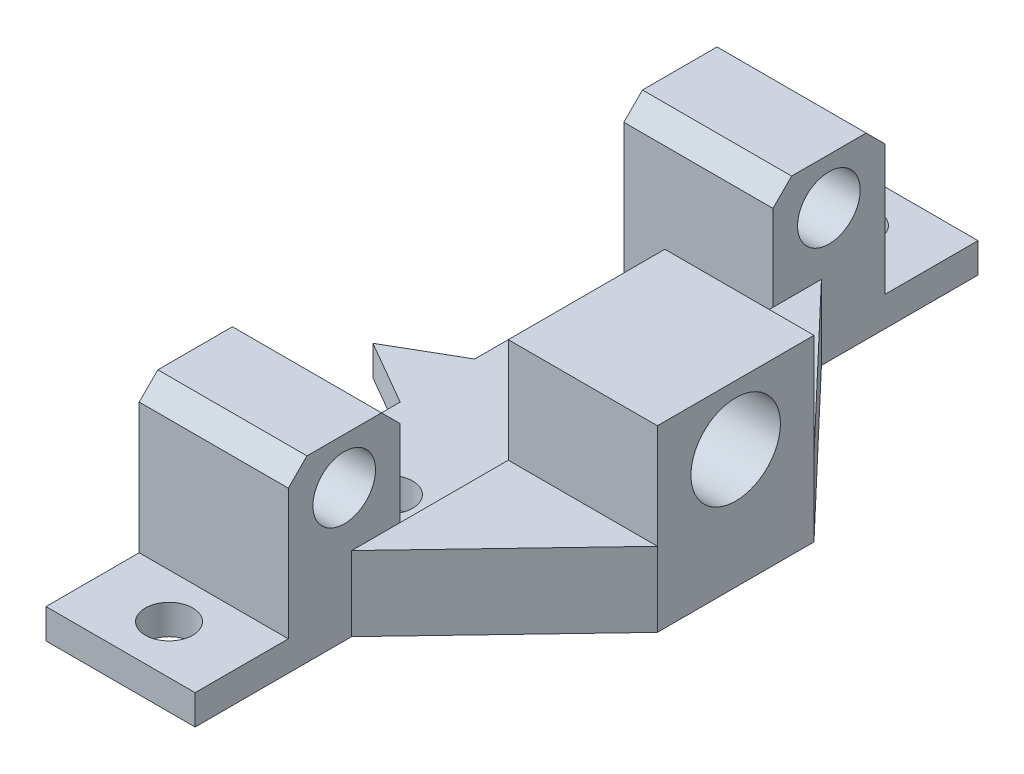
SolidWorks part; units mm, degrees
ref_plane "Front Plane" through (0, 0, 0) normal (0, 0, 1) x (1, 0, 0)
ref_plane "Top Plane" through (0, 0, 0) normal (0, 1, 0) x (1, 0, 0)
ref_plane "Right Plane" through (0, 0, 0) normal (1, 0, 0) x (0, 0, -1)
sketch "Sketch1" plane through (0, 0, 0) normal (0, 1, 0) x (1, 0, 0)
  line L1 (0, 0) -> (20, 0)
  line L2 (0, 0) -> (0, 105)
  line L3 (0, 105) -> (20, 105)
  line L4 (20, 0) -> (20, 105)
  dimension "D1" = 105
  dimension "D2" = 20
extrude "Boss-Extrude1" add sketch "Sketch1" along normal blind 4
sketch "Sketch2" plane through (0, 0, 0) normal (-1, 0, 0) x (0, 0, 1)
  line L0 (-105, 0) -> (0, 0) construction
  line L5 (-12.5, 21.5) -> (-15, 24)
  line L6 (-92.5, 0) -> (-77.5, 0)
  line L7 (-92.5, 0) -> (-92.5, 24)
  line L8 (-92.5, 24) -> (-77.5, 24)
  line L9 (-77.5, 0) -> (-77.5, 24)
  line L10 (-105, 0) -> (-92.5, 0) construction
  line L11 (-80, 24) -> (-77.5, 21.5)
  line L12 (-92.5, 21.5) -> (-90, 24)
  line L13 (-52.5, 0) -> (-52.5, 4) construction
  line L14 (-25, 24) -> (-27.5, 21.5)
  line L15 (-105, 4) -> (0, 4) construction
  line L16 (-27.5, 0) -> (-27.5, 24)
  line L17 (-12.5, 24) -> (-27.5, 24)
  line L18 (-12.5, 0) -> (-12.5, 24)
  line L19 (-12.5, 0) -> (-27.5, 0)
  circle A0 centre (-85, 17.8) radius 4.2
  circle A1 centre (-20, 17.8) radius 4.2
  point P10 (-85, 24)
  point P25 (-52.5, 4)
  point P30 (-20, 24)
  line M15 (0, 4) -> (-105, 4)
  dimension "D4" = 8.4
  dimension "D2" = 15
  dimension "D3" = 24
  dimension "D6" = 2.5
  dimension "D7" = 2.5
  dimension "D8" = 2.5
  dimension "D9" = 2.5
  dimension "D1" = 65
  dimension "D5" = 6.2
extrude "Boss-Extrude2" add sketch "Sketch2" against normal up to surface (20 mm away) contours L18 L5 L17 L14 L16 A1 M15 | L12 L7 L9 L11 L8 A0 M15 region at (0, 12.876, -20) region at (0, 12.876, -85) up to face at (20, 2, -52.5)
sketch "Sketch3" plane through (0, 0, 0) normal (0, -1, 0) x (1, 0, 0)
  line L0 (0, -57.5) -> (-8.6603, -52.5)
  line L1 (0, -105) -> (0, 0) construction
  line L2 (-8.6603, -52.5) -> (0, -47.5)
  line L3 (0, -57.5) -> (0, -47.5)
  point P6 (0, -52.5)
  dimension "D1" = 10
  dimension "D2" = 10
  dimension "D3" = 10
extrude "Boss-Extrude3" add sketch "Sketch3" against normal up to surface (4 mm away) up to face at (10, 4, -98.75)
sketch "Sketch4" plane through (0, 4, 0) normal (0, 1, 0) x (1, 0, 0)
  line L0 (10, 105) -> (10, 0) construction
  line L1 (20, 105) -> (0, 105) construction
  line L2 (0, 0) -> (20, 0) construction
  circle A0 centre (10, 98.5) radius 3.175
  circle A1 centre (10, 69) radius 3.175
  circle A2 centre (10, 36) radius 3.175
  circle A3 centre (10, 6.5) radius 3.175
  dimension "D1" = 6.35
  dimension "D2" = 6.5
  dimension "D3" = 36
  dimension "D4" = 6.5
  dimension "D5" = 36
extrude "Cut-Extrude1" cut sketch "Sketch4" against normal through all
sketch "Sketch5" plane through (20, 0, 0) normal (1, 0, 0) x (0, 0, -1)
  line L0 (0, 0) -> (105, 0) construction
  line L1 (42, 0) -> (63, 0)
  line L2 (42, 0) -> (42, 24)
  line L3 (42, 24) -> (63, 24)
  line L4 (63, 0) -> (63, 24)
  line L5 (63, 0) -> (105, 0) construction
  line L10 (25, 24) -> (15, 24) construction
  line L12 (42, 0) -> (0, 0) construction
  dimension "D1" = 21
extrude "Boss-Extrude4" add sketch "Sketch5" along normal blind 20
sketch "Sketch6" plane through (40, 0, 0) normal (1, 0, 0) x (0, 0, -1)
  line L0 (52.5, 24) -> (52.5, 0) construction
  line L1 (63, 24) -> (42, 24) construction
  line L2 (42, 0) -> (63, 0) construction
  circle A0 centre (52.5, 16) radius 6
  point P8 (52.5, 15.3114)
  dimension "D1" = 12
  dimension "D2" = 8
extrude "Cut-Extrude2" cut sketch "Sketch6" against normal through all
sketch "Sketch11" plane through (0, 0, 0) normal (0, -1, 0) x (1, 0, 0)
  line L0 (40, -63) -> (20, -84)
  line L1 (20, -63) -> (20, -105) construction
  line L2 (40, -63) -> (20, -63)
  line L3 (20, -63) -> (20, -84)
  line L4 (40, -42) -> (20, -42)
  line L5 (20, -42) -> (20, -21)
  line L7 (20, -21) -> (40, -42)
  line L8 (20, 0) -> (20, -42) construction
  point P11 (20, -25.774)
  point P15 (20, -21)
  point P16 (20, -84)
extrude "Boss-Extrude5" add sketch "Sketch11" against normal blind 10
equation "\"8mm hole\" = 8.4mm"
equation "\"D4@Sketch2\"= \"8mm hole\""
equation "\"22mm hole\"= 23mm"
equation "\"15mm hole\"= 15.8mm"
equation "\"bed height offset\"= 3mm"
equation "\"D3@Sketch2\"= 21 + \"bed height offset\""
